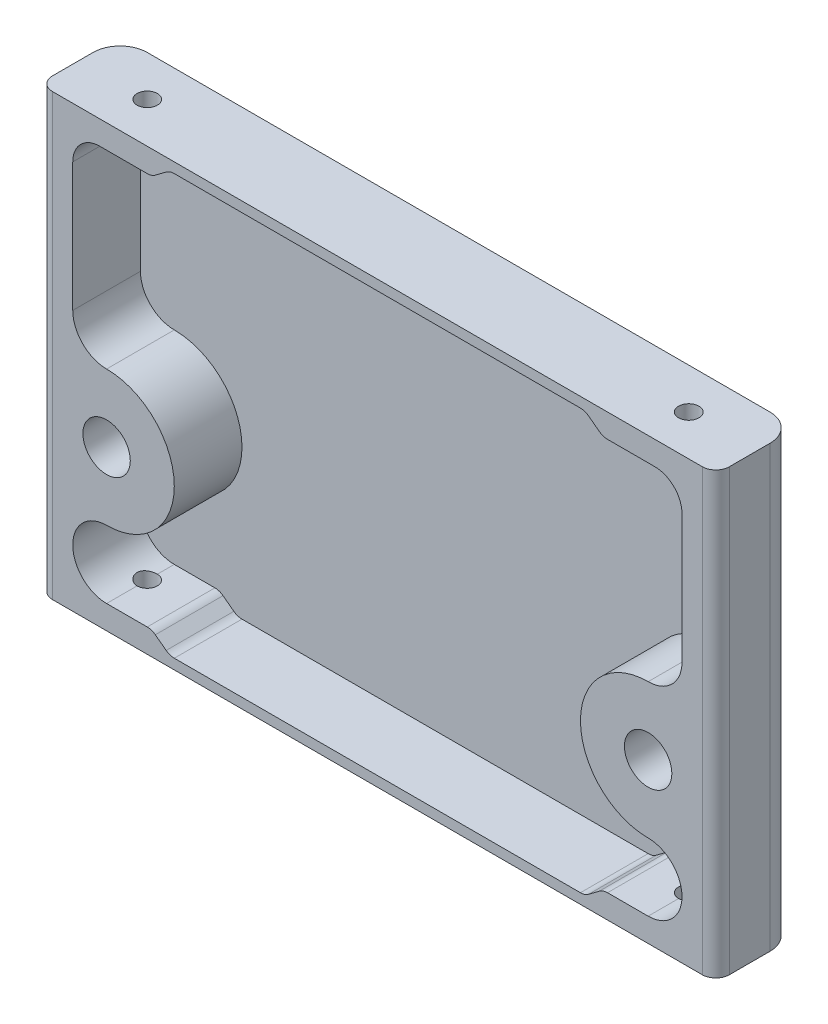
SolidWorks part; units mm, degrees
ref_plane "前视基准面" through (0, 0, 0) normal (0, 0, 1) x (1, 0, 0)
ref_plane "上视基准面" through (0, 0, 0) normal (0, 1, 0) x (1, 0, 0)
ref_plane "右视基准面" through (0, 0, 0) normal (1, 0, 0) x (0, 0, -1)
sketch "草图1" plane through (0, 0, 0) normal (0, 0, 1) x (1, 0, 0)
  line L1 (-50, -32.5) -> (50, -32.5)
  line L2 (-50, -32.5) -> (-50, 32.5)
  line L3 (-50, 32.5) -> (50, 32.5)
  line L4 (50, -32.5) -> (50, 32.5)
  line L5 (-50, -32.5) -> (50, 32.5) construction
  line L6 (-50, 32.5) -> (50, -32.5) construction
  point P0 (0, 0)
  dimension "D1" = 100
  dimension "D2" = 65
extrude "凸台-拉伸1" add sketch "草图1" along normal blind 12
sketch "草图2" plane through (0, 0, 12) normal (0, 0, 1) x (1, 0, 0)
  line L0 (0, 32.5) -> (0, -32.5) construction
  line L1 (50, 32.5) -> (-50, 32.5) construction
  line L2 (-50, -32.5) -> (50, -32.5) construction
  line L3 (30, 31) -> (-30, 31)
  line L4 (-31.2, 30.6) -> (-32.8, 29.4)
  line L5 (-34, 29) -> (-41, 29)
  line L6 (-45, 25) -> (-45, 6)
  line L7 (-40, -29) -> (-34, -29)
  line L8 (-32.8, -29.4) -> (-31.2, -30.6)
  line L9 (-30, -31) -> (30, -31)
  line L10 (-50, 32.5) -> (-50, -32.5) construction
  line L11 (32.8, -29.4) -> (31.2, -30.6)
  line L12 (40, -29) -> (34, -29)
  line L13 (45, 25) -> (45, 6)
  line L14 (34, 29) -> (41, 29)
  line L15 (31.2, 30.6) -> (32.8, 29.4)
  arc A0 (-45, 6) -> (-40, 1) centre (-40, 6) ccw
  arc A1 (-40, 1) -> (-40, -19) centre (-40, -9) cw
  arc A2 (-40, -19) -> (-40, -29) centre (-40, -24) ccw
  arc A3 (-41, 29) -> (-45, 25) centre (-41, 25) ccw
  circle A4 centre (-40, -9) radius 3.5
  circle A5 centre (40, -9) radius 3.5
  arc A6 (41, 29) -> (45, 25) centre (41, 25) cw
  arc A7 (40, -19) -> (40, -29) centre (40, -24) cw
  arc A8 (40, 1) -> (40, -19) centre (40, -9) ccw
  arc A9 (45, 6) -> (40, 1) centre (40, 6) cw
  arc A10 (-34, -29) -> (-32.8, -29.4) centre (-34, -31) cw
  arc A11 (-31.2, -30.6) -> (-30, -31) centre (-30, -29) ccw
  arc A12 (31.2, -30.6) -> (30, -31) centre (30, -29) cw
  arc A13 (32.8, -29.4) -> (34, -29) centre (34, -31) cw
  arc A14 (31.2, 30.6) -> (30, 31) centre (30, 29) ccw
  arc A15 (34, 29) -> (32.8, 29.4) centre (34, 31) cw
  arc A16 (-30, 31) -> (-31.2, 30.6) centre (-30, 29) ccw
  arc A17 (-32.8, 29.4) -> (-34, 29) centre (-34, 31) cw
  point P24 (-45, 29)
  point P25 (-33.3333, -29)
  point P30 (-30.6667, -31)
  point P33 (-45, -24)
  point P46 (0, -31)
  point P49 (0, 31)
  point P50 (30.6667, -31)
  point P53 (33.3333, -29)
  point P56 (30.6667, 31)
  point P59 (33.3333, 29)
  point P62 (-30.6667, 31)
  point P65 (-33.3333, 29)
  point P66 (0, 0)
  point P67 (0, 0)
  dimension "D5" = 4
  dimension "D8" = 7
  dimension "D9" = 10
  dimension "D10" = 23.5
  dimension "D13" = 2
  dimension "D2" = 7
  dimension "D3" = 2
  dimension "D4" = 90
  dimension "D6" = 3.5
  dimension "D7" = 62
  dimension "D11" = 1.5
  dimension "D12" = 60
extrude "切除-拉伸1" cut sketch "草图2" against normal offset from surface (10 mm away) 2 contours L0 L3 L4 L5 A3 L6 A0 A1 A2 L7 L8 L9 | L3 L0 L9 L11 L12 A7 A8 A9 L13 A6 L14 L15 region at (20.3341, 1.0008, 12) region at (-20.3341, 1.0008, 12) up to face at (0, 0, 0)
extrude "切除-拉伸2" cut sketch "草图2<3>" against normal through all contours A5 | A4 region at (40, -9, 12)
sketch "草图2<3>" plane through (0, 0, 12) normal (0, 0, 1) x (1, 0, 0) same geometry as "草图2"
sketch "草图3" plane through (0, 32.5, 0) normal (0, 1, 0) x (1, 0, 0)
  line L0 (50, -12) -> (50, 0) construction
  line L1 (50, -12) -> (-50, -12) construction
  circle A0 centre (40, -6) radius 1.5
  dimension "D1" = 3
  dimension "D2" = 10
  dimension "D3" = 6
extrude "切除-拉伸3" cut sketch "草图3" against normal blind 10
sketch "草图4" plane through (0, -32.5, 0) normal (0, -1, 0) x (1, 0, 0)
  circle A1 centre (40, 6) radius 1.5
  circle A2 centre (40, 6) radius 1.5
  dimension "D1" = 0
extrude "切除-拉伸4" cut sketch "草图4" against normal blind 10
mirror "镜向1" about plane through (0, 0, 0) normal (1, 0, 0) of "切除-拉伸4", "切除-拉伸3"
fillet "圆角2" radius 4 2 edges at (-50, 0, 0) (50, 0, 0)
fillet "圆角3" radius 2 2 edges at (-50, 0, 12) (50, 0, 12)
